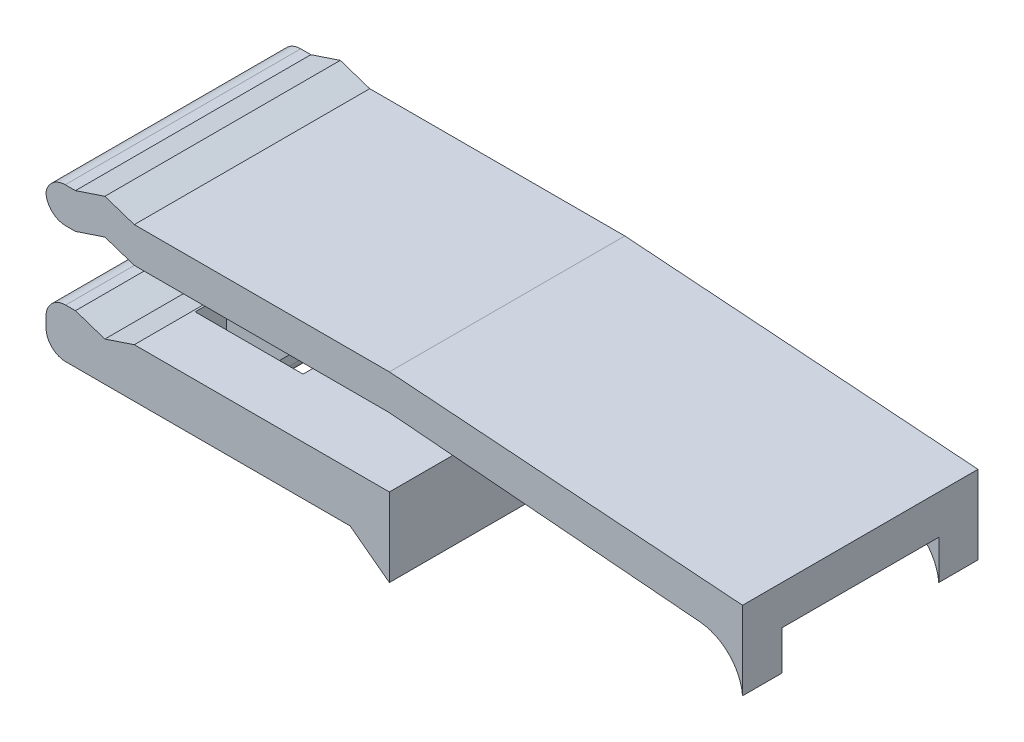
SolidWorks part; units mm, degrees
ref_plane "Front Plane" through (0, 0, 0) normal (0, 0, 1) x (1, 0, 0)
ref_plane "Top Plane" through (0, 0, 0) normal (0, 1, 0) x (1, 0, 0)
ref_plane "Right Plane" through (0, 0, 0) normal (1, 0, 0) x (0, 0, -1)
sketch "Sketch1" plane through (0, 0, 0) normal (0, 0, 1) x (1, 0, 0)
  line L0 (0, 0) -> (0, 4) construction
  line L1 (0, 0) -> (-18, 0) construction
  line L2 (0, 4) -> (-18, 5.3)
  line L3 (-18, 5.3) -> (-31, 5.3)
  line L4 (-31, 5.3) -> (-32.5, 5.8)
  line L5 (-32.5, 5.8) -> (-34, 5.3)
  line L6 (-34, 5.3) -> (-35.5, 5.3)
  line L7 (-35.5, 5.3) -> (-35.5, 3.5)
  line L8 (-35.5, -2.5) -> (-20, -2.5)
  line L9 (-20, -2.5) -> (-18, -4)
  line L10 (-35.5, 3.5) -> (-34, 3.5)
  line L11 (-34, 3.5) -> (-32.5, 4)
  line L12 (-18, 0) -> (-18, -4)
  line L13 (-18, 0) -> (-31, 0)
  line L14 (-31, 0) -> (-32.5, -0.5)
  line L15 (-32.5, -0.5) -> (-34, 0)
  line L16 (-34, 0) -> (-35.5, 0)
  line L17 (-35.5, 0) -> (-35.5, -2.5)
  line L18 (-32.5, 4) -> (-31, 3.5)
  line L19 (-31, 3.5) -> (-18, 3.5)
  line L20 (-18, 0) -> (-18, 5.3) construction
  line L21 (-18, 3.5) -> (0, 2)
  line L22 (0, 2) -> (0, 4)
  dimension "D1" = 13
  dimension "D2" = 18
  dimension "D3" = 0.5
  dimension "D4" = 2.5
  dimension "D5" = 1.5
  dimension "D6" = 3.5
  dimension "D7" = 1.5
  dimension "D8" = 2
  dimension "D9" = 0.5
  dimension "D10" = 2
  dimension "D11" = 0.5
  dimension "D12" = 1.8
  dimension "D13" = 1.5
  dimension "D15" = 3
  dimension "D16" = 1.5
extrude "Boss-Extrude1" add sketch "Sketch1" along normal blind 12
sketch "Sketch2" plane through (0, -2.5, 0) normal (0, -1, 0) x (1, 0, 0)
  line L0 (-20, 12) -> (-20, 0) construction
  line L1 (-30.9, 9) -> (-25.4, 9)
  line L2 (-30.9, 9) -> (-30.9, 3)
  line L3 (-30.9, 3) -> (-25.4, 3)
  line L4 (-25.4, 9) -> (-25.4, 3)
  line L5 (-31, 12) -> (-31, 0) construction
  line L7 (-20, 6) -> (-35.5, 6) construction
  line L8 (-35.5, 12) -> (-35.5, 0) construction
  point P9 (-25.4, 6)
  dimension "D1" = 0.1
  dimension "D2" = 5.5
  dimension "D3" = 6
extrude "Cut-Extrude1" cut sketch "Sketch2" against normal blind 3
sketch "Sketch3" plane through (0, 0, 3) normal (0, 0, 1) x (1, 0, 0)
  line L0 (-25.4, 0) -> (-27.4, -2)
  line L1 (-27.4, -2) -> (-27.4, -2.5)
  line L2 (-35.5, -2.5) -> (-20, -2.5) construction
  line L3 (-27.4, -2.5) -> (-25.4, -2.5)
  line L4 (-25.4, -2.5) -> (-25.4, 0)
  dimension "D1" = 0.5
  dimension "D2" = 2
extrude "Boss-Extrude2" add sketch "Sketch3" along normal up to surface (6 mm away) up to face at (-28.15, -1.25, 9)
sketch "Sketch4" plane through (0, 0, 12) normal (0, 0, 1) x (1, 0, 0)
  line L0 (-28.6, -2) -> (-26.6, 0)
  line L1 (-18, 0) -> (-31, 0) construction
  line L2 (-26.6, 0) -> (-26.6, 0.4)
  line L3 (-26.6, 0.4) -> (-28.1, 0.4)
  line L4 (-28.1, 0.4) -> (-28.1, 1.2)
  line L5 (-31, 3.5) -> (-18, 3.5) construction
  line L6 (-28.6, -2) -> (-28.6, -3)
  line L7 (-28.6, -3) -> (-29.8, -3)
  line L8 (-29.8, -3) -> (-29.8, 1.2)
  line L10 (-27.4, -2) -> (-27.4, -2.5) construction
  line L11 (-28.1, 1.2) -> (-30.1804, 2.4011) construction
  line L12 (-28.1, 1.2) -> (-25.8, 3.5)
  line L13 (-29.5722, 2.05) -> (-28.7351, 3.5)
  line L15 (-35.5, -2.5) -> (-20, -2.5) construction
  line L16 (-28.7351, 3.5) -> (-25.8, 3.5)
  arc A0 (-29.5722, 2.05) -> (-29.8, 1.2) centre (-28.1, 1.2) ccw
  dimension "D1" = 1.5
  dimension "D2" = 1.2
  dimension "D3" = 45
  dimension "D4" = 0.4
  dimension "D5" = 1.2
  dimension "D6" = 1
  dimension "D7" = 2
  dimension "D8" = 0.8
  dimension "D9" = 30
  dimension "D11" = 0.8
  dimension "D13" = 2.9
  dimension "D14" = 3.1
extrude "Boss-Extrude3" add sketch "Sketch4" against normal mid plane 5 from offset 6 offset against normal yes
fillet "Fillet7" radius 1 1 edges at (-35.5, 0, 6)
fillet "Fillet8" radius 1 1 edges at (-35.5, 3.5, 6)
fillet "Fillet10" radius 1 1 edges at (-35.5, 5.3, 6)
fillet "Fillet11" radius 1 1 edges at (-35.5, -2.5, 6)
sketch "Sketch5" plane through (0, 0, 12) normal (0, 0, 1) x (1, 0, 0)
  line L0 (0, 2) -> (0, 0)
  line L1 (-18, 3.5) -> (0, 2) construction
  line L2 (-2.1818, 2.1818) -> (0, 2)
  arc A0 (-2.1818, 2.1818) -> (0, 0) centre (-2.3802, -0.1983) cw
extrude "Boss-Extrude4" add sketch "Sketch5" against normal blind 2
extrude "Boss-Extrude5" add sketch "Sketch5<2>" along normal blind 2 from offset 12 offset against normal yes
sketch "Sketch5<2>" plane through (0, 0, 12) normal (0, 0, 1) x (1, 0, 0) same geometry as "Sketch5"
fillet "Fillet12" radius 0.5 2 edges at (-28.6, -3, 6) (-29.8, -3, 6)
fillet "Fillet13" radius 0.5 1 edges at (-28.1, 1.2, 6)
